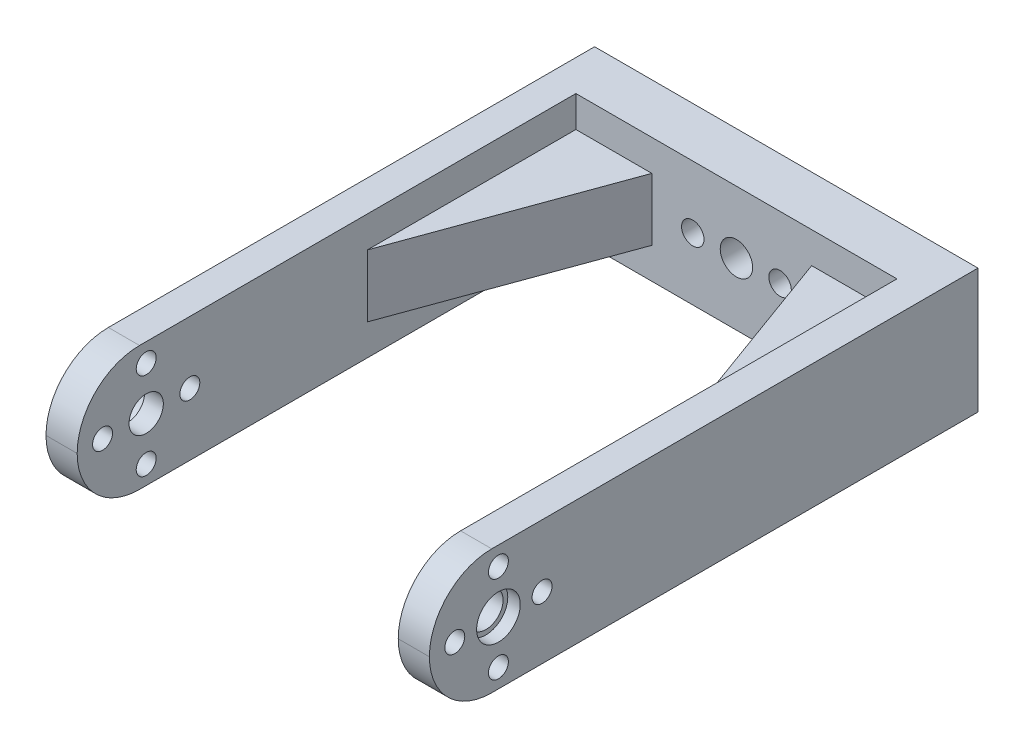
SolidWorks part; units mm, degrees
material "Plastique personnalisé"
ref_plane "Plan de face" through (0, 0, 0) normal (0, 0, 1) x (1, 0, 0)
ref_plane "Plan de dessus" through (0, 0, 0) normal (0, 1, 0) x (1, 0, 0)
ref_plane "Plan de droite" through (0, 0, 0) normal (1, 0, 0) x (0, 0, -1)
sketch "Esquisse1" plane through (0, 0, 0) normal (0, 0, 1) x (1, 0, 0)
  line L0 (5, 20) -> (5, 0)
  line L1 (0, 0) -> (61.5, 0)
  line L2 (0, 0) -> (0, 20)
  line L3 (0, 20) -> (61.5, 20)
  line L4 (61.5, 0) -> (61.5, 20)
  line L5 (56.5, 20) -> (56.5, 0)
  dimension "D1" = 61.5
  dimension "D2" = 5
  dimension "20" = 20
  dimension "D3" = 5
extrude "Boss.-Extru.1" add sketch "Esquisse1" along normal blind 80 contours L3 L2 L1 L0 | L3 L5 L1 L4 region at (2.5, 10, 0) region at (59, 10, 0)
extrude "Boss.-Extru.2" add sketch "Esquisse1<3>" against normal blind 8 contours L3 L4 L1 L2
sketch "Esquisse1<3>" plane through (0, 0, 0) normal (0, 0, 1) x (1, 0, 0) same geometry as "Esquisse1"
sketch "Esquisse3" plane through (61.5, 0, 0) normal (1, 0, 0) x (0, 0, -1)
  line L0 (-80, 10) -> (8, 10) construction
  line L1 (-80, 0) -> (-80, 20) construction
  line L2 (8, 0) -> (8, 20) construction
  line L8 (-68.9279, 10) -> (-68.9279, 18.5318) construction
  line L9 (-68.9279, 10) -> (-68.9279, 1.2804) construction
  circle A1 centre (-68.9279, 10) radius 2.75
  dimension "D1" = 11.0721
  dimension "D2" = 5.5
extrude "Enlèv. mat.-Extru.2" cut sketch "Esquisse3" against normal blind 85 contours A1
sketch "Esquisse4" plane through (0, 0, -8) normal (0, 0, -1) x (-1, 0, 0)
  line L0 (-61.5, 10) -> (0, 10) construction
  line L1 (-61.5, 0) -> (-61.5, 20) construction
  line L2 (0, 0) -> (0, 20) construction
  line L3 (-61.5, 0) -> (-61.5, 20) construction
  line L4 (-30.75, 10) -> (-30.75, 20) construction
  line L5 (-30.75, 10) -> (-30.75, -6.6857) construction
  line L6 (0, 20) -> (-61.5, 20) construction
  circle A1 centre (-30.75, 10) radius 2.6
  circle A5 centre (-37.75, 10) radius 1.8
  circle A6 centre (-23.75, 10) radius 1.8
  point P6 (-61.5, 10)
  point P15 (0, 10)
  dimension "D2" = 5.2
  dimension "D3" = 3.6
  dimension "D1" = 7
extrude "Enlèv. mat.-Extru.3" cut sketch "Esquisse4" against normal blind 10 contours A1 | A6 | A5 region at (30.75, 10, -8) region at (23.75, 10, -8)
fillet "Congé4" radius 10 4 edges at (2.5, 20, 80) (2.5, 0, 80) (59, 0, 80) (59, 20, 80)
sketch "Esquisse6" plane through (0, 0, 0) normal (1, 0, 0) x (0, 0, -1)
  line L0 (-68.9279, 12.75) -> (-68.9279, 7.25) construction
  line L1 (-80, 10) -> (8, 10) construction
  line L3 (-68.9279, 0) -> (-68.9279, 50) construction
  line L4 (8, 0) -> (-70, 0) construction
  line L5 (8, 0) -> (8, 20) construction
  circle A0 centre (-75.9279, 10) radius 1.6
  circle A4 centre (-68.9279, 17) radius 1.6
  circle A5 centre (-61.9279, 10) radius 1.6
  circle A6 centre (-68.9279, 3) radius 1.6
  circle A7 centre (-68.9279, 10) radius 2.75 construction
  arc A8 (-70, 20) -> (-80, 10) centre (-70, 10) ccw construction
  point P2 (-68.9279, 10)
  point P12 (-68.9279, 10)
  dimension "D1" = 3.2
  dimension "D2" = 4
  dimension "D3" = 7
extrude "Trous palonnier GrabCAD M3 entraxe 14" cut sketch "Esquisse6" along normal through all
ref_plane "Plan1" through (0, 10, 0) normal (0, -1, 0) x (-1, 0, 0)
sketch "Esquisse9" plane through (0, 10, 0) normal (0, -1, 0) x (-1, 0, 0)
  line L1 (-42.8192, 0) -> (-56.5, -37.5877)
  line L2 (-56.5, -70) -> (-56.5, 0) construction
  line L3 (-5, 0) -> (-56.5, 0) construction
  dimension "D1" = 40
  dimension "D2" = 70
rib "Nervure2" sketch "Esquisse9" sketch "Esquisse9" thickness 10 extrusion direction parallel to sketch draft on no parameters "D1"=10
ref_plane "Plan2" through (30, 0, 0) normal (-1, 0, 0) x (0, 0, 1)
mirror "Symétrie1" about plane through (30, 0, 0) normal (-1, 0, 0) of "Nervure2"
sketch "Esquisse10" plane through (61.5, 0, 0) normal (1, 0, 0) x (0, 0, -1)
  circle A0 centre (-68.9279, 10) radius 3.5
  dimension "D1" = 7
extrude "Enlèv. mat.-Extru.4" cut sketch "Esquisse10" against normal blind 2
sketch "Esquisse11" plane through (0, 0, 0) normal (-1, 0, 0) x (0, 0, 1)
  circle A0 centre (68.9279, 10) radius 3.5
  dimension "D1" = 7
extrude "Enlèv. mat.-Extru.5" cut sketch "Esquisse11" against normal blind 2
